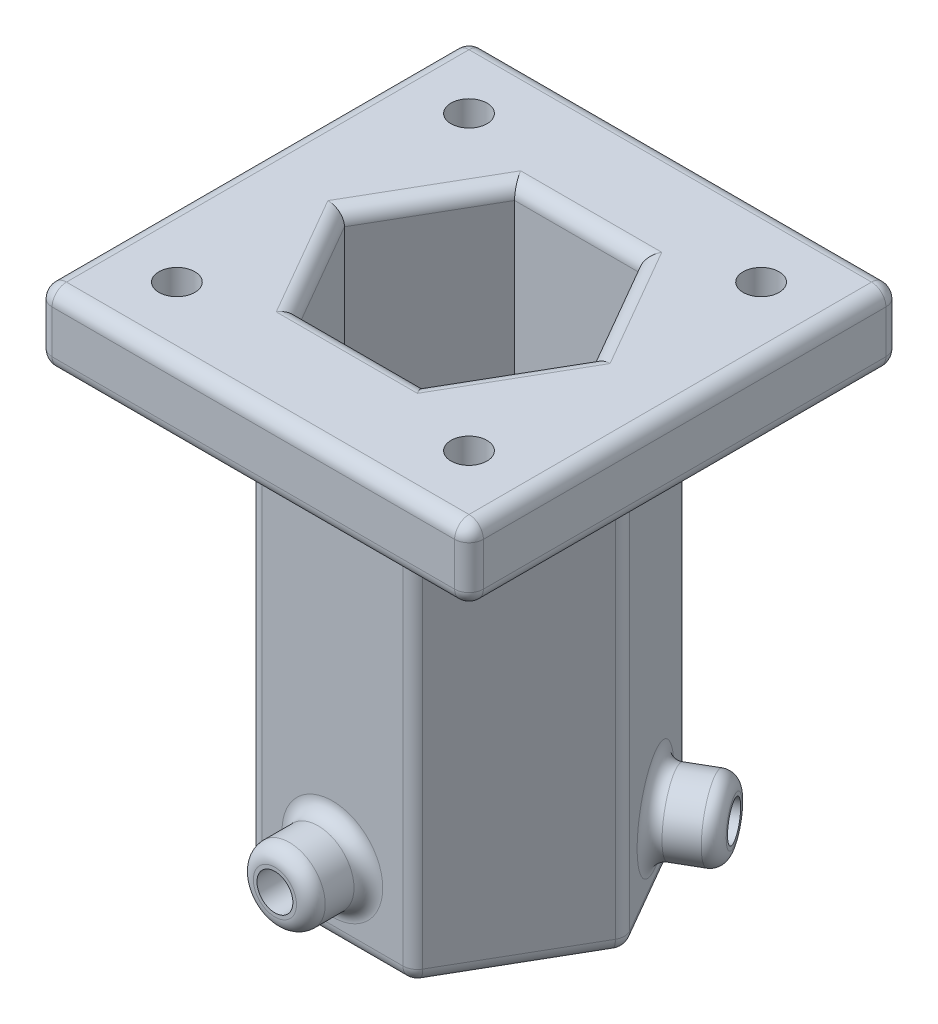
SolidWorks part; units mm, degrees
ref_plane "Front Plane" through (0, 0, 0) normal (0, 0, 1) x (1, 0, 0)
ref_plane "Top Plane" through (0, 0, 0) normal (0, 1, 0) x (1, 0, 0)
ref_plane "Right Plane" through (0, 0, 0) normal (1, 0, 0) x (0, 0, -1)
sketch "Sketch1" plane through (0, 0, 0) normal (0, 1, 0) x (1, 0, 0)
  line L1 (0, 0) -> (30, 0)
  line L2 (0, 0) -> (0, 30)
  line L3 (0, 30) -> (30, 30)
  line L4 (30, 0) -> (30, 30)
  dimension "D1" = 30
extrude "Body" add sketch "Sketch1" along normal blind 5 contours L4 L3 L2 L1
sketch "Sketch2" plane through (0, 5, 0) normal (0, 1, 0) x (1, 0, 0)
  line L0 (15, 3.6661) -> (15, 26.3339) construction
  line L1 (25.9697, 15) -> (20.4848, 24.5)
  line L2 (20.4848, 24.5) -> (9.5152, 24.5)
  line L3 (9.5152, 24.5) -> (4.0303, 15)
  line L4 (4.0303, 15) -> (9.5152, 5.5)
  line L5 (9.5152, 5.5) -> (20.4848, 5.5)
  line L6 (20.4848, 5.5) -> (25.9697, 15)
  line L7 (24.2468, 15) -> (5.7532, 15) construction
  line L12 (0, 0) -> (0, 30) construction
  line L13 (30, 0) -> (30, 30) construction
  line L14 (0, 30) -> (30, 30) construction
  line L15 (0, 0) -> (30, 0) construction
  circle A0 centre (15, 15) radius 9.5 construction
  dimension "D1" = 19
extrude "Shaft" add sketch "Sketch2" against normal blind 35 contours L2 L3 L4 L5 L6 L1
sketch "Sketch3" plane through (0, 5, 0) normal (0, 1, 0) x (1, 0, 0)
  line L0 (20.4848, 24.5) -> (9.5152, 24.5) construction
  line L1 (23.6603, 15) -> (19.3301, 22.5)
  line L2 (19.3301, 22.5) -> (10.6699, 22.5)
  line L3 (10.6699, 22.5) -> (6.3397, 15)
  line L4 (6.3397, 15) -> (10.6699, 7.5)
  line L5 (10.6699, 7.5) -> (19.3301, 7.5)
  line L6 (19.3301, 7.5) -> (23.6603, 15)
  circle A0 centre (15, 15) radius 7.5 construction
  dimension "D1" = 15
extrude "ShaftHole" cut sketch "Sketch3" against normal through all
sketch "MountHoleLoc" plane through (-1.7404, 0, -1.0048) normal (0.866, 0, 0.5) x (0.5, 0, -0.866)
  line L0 (20.4904, -17.2414) -> (20.4904, -32.7586) construction
  line L2 (25.9752, -30) -> (15.0056, -30) construction
  line L5 (24.8205, -30) -> (24.8205, 5) construction
  line L6 (16.1603, -30) -> (16.1603, 5) construction
  point P0 (20.4904, -25)
  dimension "D1" = 5
sketch "Sketch5" plane through (-1.7404, 0, -1.0048) normal (0.866, 0, 0.5) x (0.5, 0, -0.866)
  circle A0 centre (20.4904, -25) radius 2.5
  dimension "D1" = 5
extrude "MountShell" add sketch "Sketch5" against normal blind 6
hole_wizard "MountHole" positions "3DSketch1" profile "Sketch6" hole size "Ø2.5" standard "ANSI Metric" end condition up to next
sketch3d "3DSketch1"
  point P0 (8.5048, -25, -18.75)
sketch "Sketch6" plane through (8.5048, -25, -18.75) normal (0, 1, 0) x (0.5, 0, -0.866)
  line L0 (0, 0) -> (0, 8.1664)
  line L1 (0, 8.1664) -> (1.25, 8.1664)
  line L2 (1.25, 8.1664) -> (1.25, 0)
  line L5 (1.25, 0) -> (0, 0)
  line L11 (0, -6.35) -> (0, 107.95) construction
  dimension "Thru Hole Dia." = 2.5
  dimension "Thru Hole Depth" = 8.1664
sketch "Sketch7" plane through (0, 5, 0) normal (0, 1, 0) x (1, 0, 0)
  line L0 (6.3397, 15) -> (23.6603, 15) construction
  point P4 (15, 15)
ref_axis "Axis1" through (15, 5, -15) along (0, 1, 0)
pattern_circular "CirPattern1" count 3 over 360 about axis through (15, 5, -15) along (0, 1, 0) of "MountShell", "MountHole"
sketch "MountingHoleLoc" plane through (0, 5, 0) normal (0, 1, 0) x (1, 0, 0)
  point P0 (4.84, 25.16)
  dimension "D1" = 10.16
  dimension "D2" = 10.16
hole_wizard "MountingHoles" positions "3DSketch2" profile "Sketch11" hole size "Ø2.5" standard "ANSI Metric" end condition up to next
sketch3d "3DSketch2"
  point P0 (4.84, 5, -25.16)
sketch "Sketch11" plane through (4.84, 5, -25.16) normal (1, 0, 0) x (0, 0, 1)
  line L0 (0, 0) -> (0, 5.001)
  line L1 (0, 5.001) -> (1.25, 5.001)
  line L2 (1.25, 5.001) -> (1.25, 0)
  line L5 (1.25, 0) -> (0, 0)
  line L11 (0, -6.35) -> (0, 107.95) construction
  dimension "Thru Hole Dia." = 2.5
  dimension "Thru Hole Depth" = 5.001
pattern_linear "LPattern1" count 2 spacing 20.32 along (0, 0, 1) count 2 spacing 20.32 along (1, 0, 0) of "MountingHoles"
fillet "Fillet1" radius 1 48 edges at (0, 5, -15) (15, 5, -30) (0, 2.5, -30) (30, 5, -15) (30, 2.5, -30) (0, 2.5, 0) (15, 5, 0) (30, 2.5, 0) (15, -30, -5.5) (17.5, -25, -5.5) (23.2272, -30, -10.25) (20.4848, -15, -5.5) (23.2272, -30, -19.75) (25.9697, -15, -15) (21.9772, -25, -21.9151) (15, -30, -24.5) (20.4848, -15, -24.5) (6.7728, -30, -19.75) (9.5152, -15, -24.5) (5.5228, -25, -17.5849) (9.5152, -15, -5.5) (6.7728, -30, -10.25) (4.0303, -15, -15) (30, 0, -15) (15, 0, -30) (0, 0, -15) (15, 0, 0) (15, 0, -5.5) (6.7728, 0, -10.25) (6.7728, 0, -19.75) (15, 0, -24.5) (23.2272, 0, -19.75) (23.2272, 0, -10.25) (12.5, -25, -1.5) (8.5048, -30, -11.25) (8.5048, -30, -18.75) (15, -30, -22.5) (21.4952, -30, -18.75) (21.4952, -30, -11.25) (15, -30, -7.5) (4.5587, -25, -23.9151) (27.9413, -25, -19.5849) (8.5048, 5, -11.25) (8.5048, 5, -18.75) (15, 5, -22.5) (21.4952, 5, -18.75) (21.4952, 5, -11.25) (15, 5, -7.5)
equation "\"MOTOR_D\"= 28"
equation "\"MOTOR_H\"= 19"
equation "\"SHAFT_CENTER_OFF\"= 8"
equation "\"SLIPRING_D\" = 12.4"
equation "\"PITCH_D\"= 44.45"
equation "\"HEX_D\"= 12.7"
equation "\"BODY_THICK\"= 3"
equation "\"TAP_HOLE\" = 2.5"
equation "\"SCREW_HOLE\" = 3"
equation "\"BEARING_OD\" = 28.575"
equation "\"BEARING_ID\" = 12.7"
equation "\"BEARING_THICK\" = 7.925"
equation "\"STAND_R\" = 3"
equation "\"CB_W\" = 5"
equation "\"CW_DEPTH\" = 1"
equation "\"PIN_SPACING\" = 2.54"
equation "\"PIN_D\" = 1"
equation "\"MBOARD_ZSPACE\"= 7*\"PIN_SPACING\""
equation "\"MBOARD_XSPACE\"= 7*\"PIN_SPACING\""
equation "\"MBOARD_SCREWX\"= 4"
equation "\"MBOARD_ID\"= 15"
equation "\"MBOARD_OD\"= 4 + \"MBOARD_ID\""
equation "\"D1@Sketch2\" = \"BMOUNT_HEXID\" + 2 * \"BMOUNT_HEXTHICK\""
equation "\"D1@Sketch3\" = \"BMOUNT_HEXID\""
equation "\"D1@MountShell\" = \"BMOUNT_HEXTHICK\" + 4"
equation "\"D3@LPattern1\"=\"BMOUNT_HOLEZ\" * 2"
equation "\"D4@LPattern1\"=\"BMOUNT_HOLEX\" * 2"
equation "\"PCB_THICK\" = 1.5"
equation "\"SHAFTBASE_ID\"= 12.7"
equation "\"SHAFTBASE_OD\"= \"SHAFTBASE_ID\" + 3"
equation "\"D1@Shaft\"=\"BMOUNT_HEXH\""
equation "\"COLLAR_OD\" = 20.5"
equation "\"BEARSHAFT_HOLEH\"= 10"
equation "\"SHAFT_D\" = 18"
equation "\"MOUNTHOLE_DIST\"= 4*\"PIN_SPACING\""
equation "\"D2@MountingHoleLoc\"=\"BMOUNT_HOLEX\""
equation "\"MOTOR_HOLEDIST\"= 35"
equation "\"SLIPRING_MOUNTOD\" = 15"
equation "\"SLIPRING_MOUNTTHICK\" = 8"
equation "\"SLIPRING_MOUNT_LEGH\" = 12"
equation "\"BODY_Y\"= 70"
equation "\"BODY_X\"= 60"
equation "\"BODY_Z\"= 120"
equation "\"BODY_TOPTHICK\"= 4"
equation "\"STAND_ZOFF\" = 10"
equation "\"STAND_XOFF\" = 5"
equation "\"MOTOR_ZOFF\" = 25"
equation "\"MOTOR_MOUNTANGLE\" = 120"
equation "\"DRVR_Y\" = 31"
equation "\"DRVR_Z\" = 27"
equation "\"DRVR_YOFF\" = 15"
equation "\"DRVR_ARDOFF\" = 10"
equation "\"BEARING_FLANGE_D\" = 31.242"
equation "\"BEARING_FLANGETHICK\" = 1.575"
equation "\"BMOUNT_X\" = 30"
equation "\"MBOARD_LXSPACE\"= 1*\"PIN_SPACING\""
equation "\"HEXSHAFT_D\" = 12.75"
equation "\"HEXSHAFT_FILLET\" = 2.5"
equation "\"BMOUNT_HEXID\" = 15"
equation "\"BMOUNT_HEXTHICK\" = 2"
equation "\"BMOUNT_HOLEX\" = 4*\"PIN_SPACING\""
equation "\"BMOUNT_HOLEZ\" = 4*\"PIN_SPACING\""
equation "\"BMOUNT_SCREWH\" = 5"
equation "\"BMOUNT_HEXH\" = 35"
equation "\"D1@MountHoleLoc\"=\"BMOUNT_SCREWH\""
